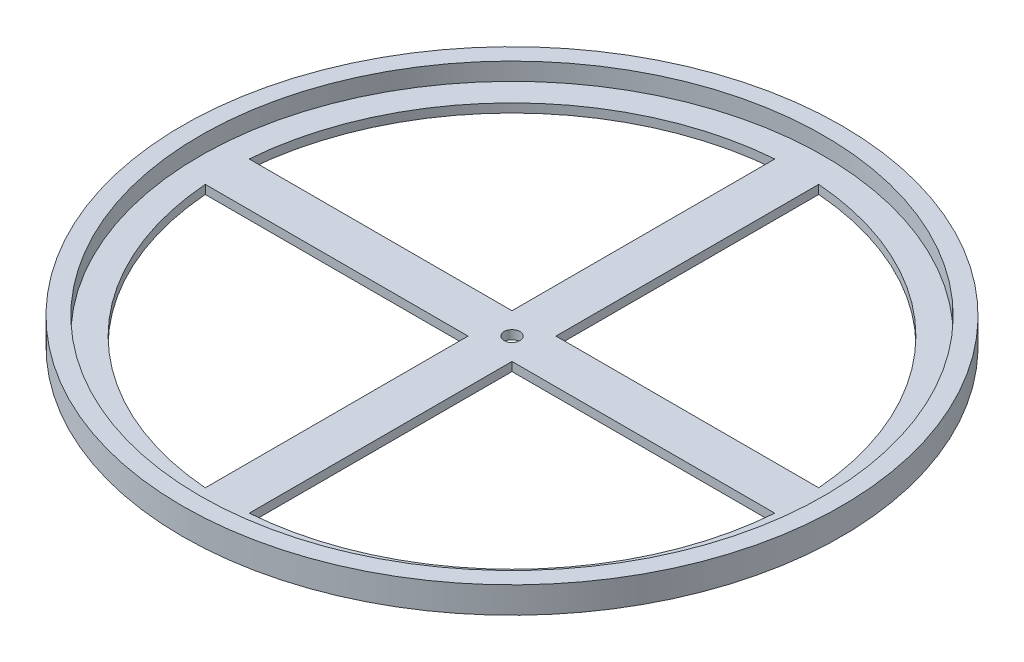
SolidWorks part; units mm, degrees
ref_plane "Front Plane" through (0, 0, 0) normal (0, 0, 1) x (1, 0, 0)
ref_plane "Top Plane" through (0, 0, 0) normal (0, 1, 0) x (1, 0, 0)
ref_plane "Right Plane" through (0, 0, 0) normal (1, 0, 0) x (0, 0, -1)
sketch "Sketch1" plane through (0, 0, 0) normal (0, 1, 0) x (1, 0, 0)
  line L0 (-2.5, 32.4037) -> (-2.5, -32.4037)
  line L1 (2.5, 32.4037) -> (2.5, -32.4037)
  line L2 (-32.4037, 2.5) -> (32.4037, 2.5)
  line L3 (-32.4037, -2.5) -> (32.4037, -2.5)
  circle A0 centre (0, 0) radius 37.5
  circle A1 centre (0, 0) radius 0.9
  circle A2 centre (0, 0) radius 32.5
  dimension "D1" = 1.8
  dimension "D2" = 75
  dimension "D3" = 65
  dimension "D4" = 5
extrude "Boss-Extrude1" add sketch "Sketch1" along normal blind 1 contours A0 A2 | L1 A2 L0 L2 | L0 A2 L1 L3 | L2 A2 L3 L0 | L3 A2 L2 L1 | L0 L3 L1 L2 A1 region at (0, 0, -17.484) region at (0, 0, -2.4293) region at (-17.484, 0, 0) region at (0, 0, 17.484) region at (17.484, 0, 0) region at (-36.4393, 0, 0)
sketch "Sketch2" plane through (0, 1, 0) normal (0, 1, 0) x (1, 0, 0)
  circle A0 centre (0, 0) radius 37.5 construction
  circle A1 centre (0, 0) radius 37.5
  circle A2 centre (0, 0) radius 35.5
  dimension "D1" = 71
extrude "Boss-Extrude2" add sketch "Sketch2" along normal blind 2
